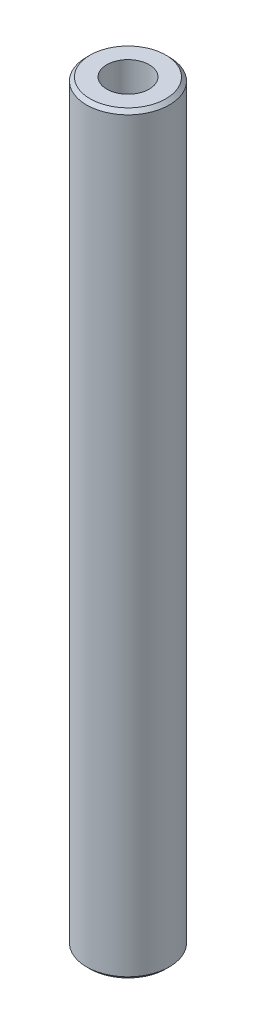
SolidWorks part; units mm, degrees
ref_plane "Front Plane" through (0, 0, 0) normal (0, 0, 1) x (1, 0, 0)
ref_plane "Top Plane" through (0, 0, 0) normal (0, 1, 0) x (1, 0, 0)
ref_plane "Right Plane" through (0, 0, 0) normal (1, 0, 0) x (0, 0, -1)
sketch "Sketch1" plane through (0, 0, 0) normal (0, 1, 0) x (1, 0, 0)
  circle A0 centre (0, 0) radius 27.5
  dimension "SHAFT_OD" = 55
extrude "Boss-Extrude1" add sketch "Sketch1" along normal blind 500.2112
sketch "Sketch2" plane through (0, 0, 0) normal (0, 1, 0) x (1, 0, 0)
  circle A0 centre (0, 0) radius 14.0832
  dimension "BORE_D" = 28.1665
extrude "Cut-Extrude1" cut sketch "Sketch2" along normal through all
chamfer "Chamfer1" distance 2.3558 angle 45 2 edges at (0, 500.2112, 27.5) (0, 0, 27.5)
